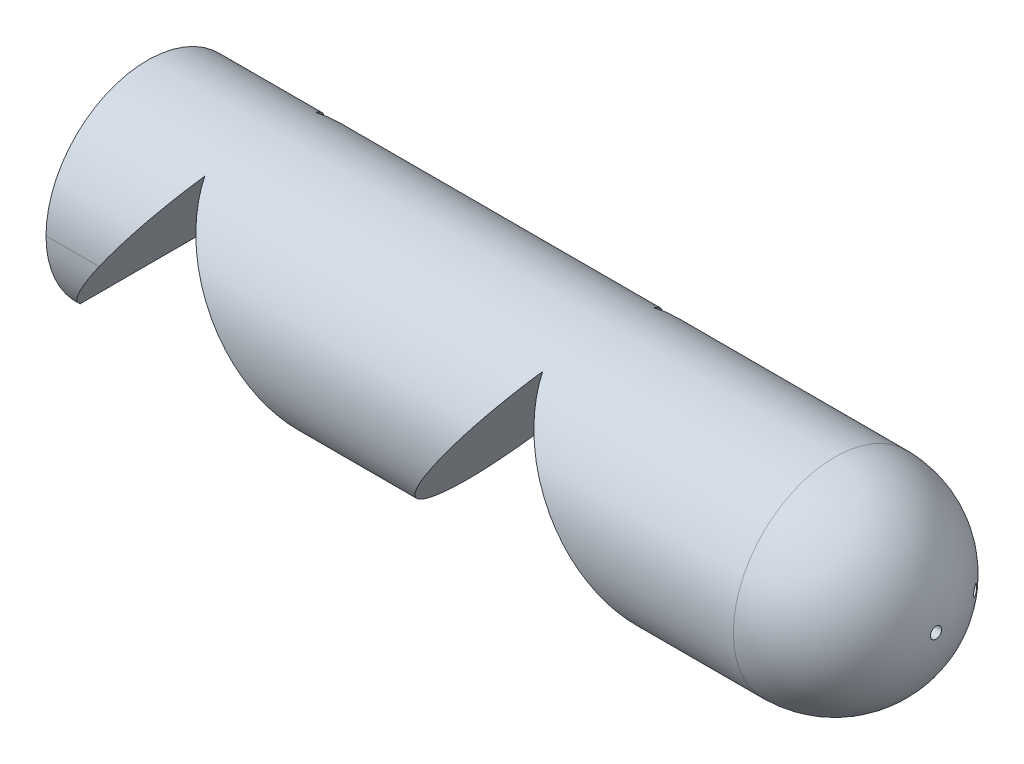
SolidWorks part; units mm, degrees
ref_plane "Front Plane" through (0, 0, 0) normal (0, 0, 1) x (1, 0, 0)
ref_plane "Top Plane" through (0, 0, 0) normal (0, 1, 0) x (1, 0, 0)
ref_plane "Right Plane" through (0, 0, 0) normal (1, 0, 0) x (0, 0, -1)
sketch "Sketch1" plane through (0, 0, 0) normal (0, 0, 1) x (1, 0, 0)
  line L1 (0, 0) -> (70, 0)
  line L2 (0, 0) -> (0, 9)
  line L3 (0, 9) -> (70, 9)
  line L4 (70, 0) -> (70, 9)
  dimension "D1" = 70
  dimension "D2" = 9
revolve "Revolve1" add sketch "Sketch1" angle 360 about L3
fillet "Fillet1" radius 9 1 edges at (70, 9, 9)
sketch "Sketch2" plane through (0, 0, 0) normal (0, 0, 1) x (1, 0, 0)
  line L0 (0, 0) -> (70, 0)
  line L1 (40, 0) -> (40, 16.5429)
  line L2 (40, 16.5429) -> (51.5835, 0)
  line L3 (40, 16.5429) -> (28.4165, 0)
  line L4 (10, 0) -> (10, 16.5429)
  line L5 (10, 16.5429) -> (21.5835, 0)
  line L6 (28.4165, 0) -> (51.5835, 0)
  line L7 (10, 16.5429) -> (-1.5835, 0)
  line L8 (-1.5835, 0) -> (21.5835, 0)
  dimension "D1" = 30
  dimension "D2" = 70
  dimension "D3" = 35
  dimension "D4" = 2
extrude "Cut-Extrude1" cut sketch "Sketch2" against normal mid plane 30 contours L1 L3 L0 | L2 L1 L0 | L0 | L5 L8 L7 region at (36.1388, 5.5143, 0) region at (13.8612, 5.5143, 0) region at (43.8612, 5.5143, 0)
ref_plane "Plane1" through (0, 0, 0) normal (-1, 0, 0) x (0, 0, 1)
sketch "Sketch4" plane through (0, 0, 0) normal (-1, 0, 0) x (0, 0, 1)
  line L0 (-5, 9) -> (5, 9) construction
  circle A0 centre (0, 9) radius 0.2
  circle A2 centre (0, 9) radius 0.2
  circle A3 centre (-5, 9) radius 0.2
  circle A4 centre (5, 9) radius 0.2 [skipped]
  point P5 (0, 9)
  dimension "D1" = 0.4
  dimension "D2" = 10
  dimension "D3" = 2
  dimension "D4" = 2
extrude "Cut-Extrude2" cut sketch "Sketch4" against normal through all contours A3 | L0 A2 | A0 L0 region at (0, 9.0849, 0) region at (0, 8.9151, 0) region at (0, 9, -5.1943)
ref_plane "Plane2" through (69.9978, 0, 0) normal (1, 0, 0) x (0, 0, -1)
sketch "Sketch5" plane through (69.9978, 0, 0) normal (1, 0, 0) x (0, 0, -1)
  circle A1 centre (0, 9) radius 0.5
  circle A2 centre (5, 9) radius 0.5
extrude "Cut-Extrude3" cut sketch "Sketch5" against normal blind 5 draft 3
